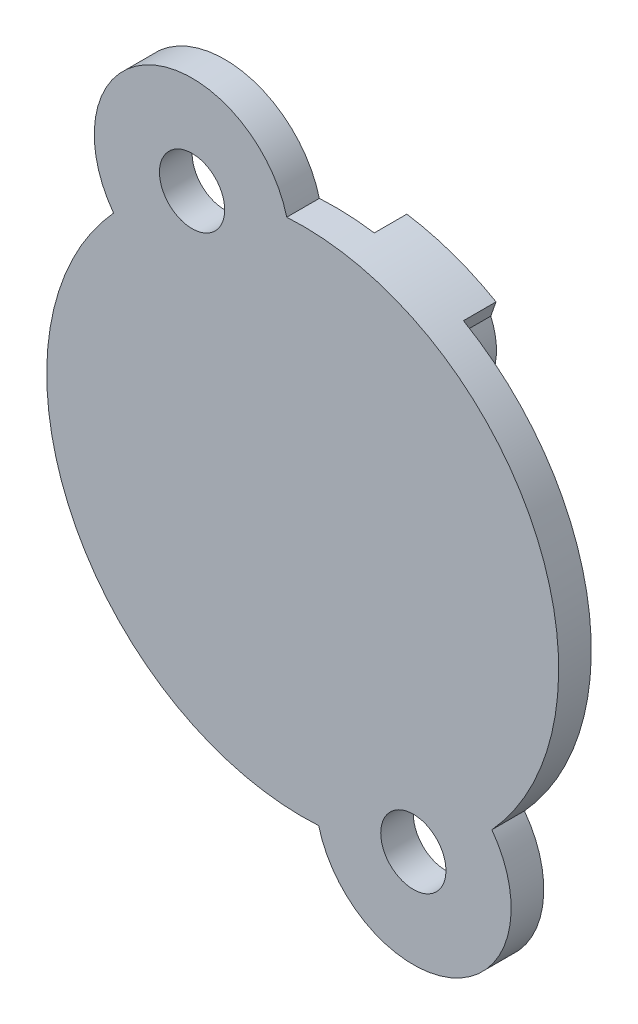
SolidWorks part; units mm, degrees
ref_plane "Front Plane" through (0, 0, 0) normal (0, 0, 1) x (1, 0, 0)
ref_plane "Top Plane" through (0, 0, 0) normal (0, 1, 0) x (1, 0, 0)
ref_plane "Right Plane" through (0, 0, 0) normal (1, 0, 0) x (0, 0, -1)
sketch "Sketch1" plane through (0, 0, 0) normal (0, 0, 1) x (1, 0, 0)
  circle A0 centre (0, 0) radius 7.85
  dimension "D1" = 15.7
extrude "Boss-Extrude1" add sketch "Sketch1" along normal blind 1
sketch "Sketch2" plane through (0, 0, 0) normal (0, 0, -1) x (-1, 0, 0)
  circle A0 centre (3.3929, 7.0789) radius 1 construction
  arc A1 (5.8006, 5.2892) -> (0.4896, 7.8347) centre (3.3929, 7.0789) ccw construction
  circle A2 centre (-3.3929, -7.0789) radius 1 construction
  arc A3 (-5.8006, -5.2892) -> (-0.4896, -7.8347) centre (-3.3929, -7.0789) ccw construction
  circle A4 centre (3.3929, 7.0789) radius 1
  arc A5 (5.8006, 5.2892) -> (0.4896, 7.8347) centre (3.3929, 7.0789) ccw
  circle A6 centre (-3.3929, -7.0789) radius 1
  arc A7 (-5.8006, -5.2892) -> (-0.4896, -7.8347) centre (-3.3929, -7.0789) ccw
  circle M1 centre (0, 0) radius 7.85
sketch "Sketch3" plane through (0, 0, 0) normal (0, 0, -1) x (-1, 0, 0)
  line L0 (-3.7675, 6.336) -> (-3.9293, 6.7958) construction
  line L1 (-3.7675, 6.336) -> (-3.9293, 6.7958)
  line L2 (-1.032, 7.2989) -> (-1.1939, 7.7587) construction
  line L3 (-1.032, 7.2989) -> (-1.1939, 7.7587)
  line L7 (1.1939, -7.7587) -> (1.032, -7.2989) construction
  line L8 (3.9293, -6.7958) -> (3.7675, -6.336) construction
  line L9 (1.1939, -7.7587) -> (1.032, -7.2989)
  line L10 (3.9293, -6.7958) -> (3.7675, -6.336)
  circle A0 centre (0, 0) radius 6
  arc A1 (-5.8006, -5.2892) -> (-0.4896, -7.8347) centre (-3.3929, -7.0789) ccw construction
  arc A2 (-5.8006, -5.2892) -> (-0.4896, -7.8347) centre (-3.3929, -7.0789) ccw
  arc A3 (5.8006, 5.2892) -> (0.4896, 7.8347) centre (3.3929, 7.0789) ccw construction
  arc A4 (5.8006, 5.2892) -> (0.4896, 7.8347) centre (3.3929, 7.0789) ccw
  circle A5 centre (3.3929, 7.0789) radius 1 construction
  circle A6 centre (3.3929, 7.0789) radius 1
  circle A7 centre (-3.3929, -7.0789) radius 1 construction
  circle A8 centre (-3.3929, -7.0789) radius 1
  circle A9 centre (0, 0) radius 7.85 construction
  circle A10 centre (0, 0) radius 7.85
  circle A11 centre (0, 0) radius 4.5
  arc A12 (-3.7675, 6.336) -> (-3.7573, 4.6779) centre (-1.9424, 5.5181) ccw construction
  arc A13 (-3.7675, 6.336) -> (-3.7573, 4.6779) centre (-1.9424, 5.5181) ccw
  arc A14 (-0.0013, 6) -> (-1.032, 7.2989) centre (-1.9424, 5.5181) ccw construction
  arc A15 (-0.0013, 6) -> (-1.032, 7.2989) centre (-1.9424, 5.5181) ccw
  arc A16 (3.7675, -6.336) -> (3.7573, -4.6779) centre (1.9424, -5.5181) ccw construction
  arc A17 (0.0013, -6) -> (1.032, -7.2989) centre (1.9424, -5.5181) ccw construction
  arc A18 (3.7675, -6.336) -> (3.7573, -4.6779) centre (1.9424, -5.5181) ccw
  arc A19 (0.0013, -6) -> (1.032, -7.2989) centre (1.9424, -5.5181) ccw
  circle M12 centre (0, 0) radius 7.85
  dimension "D1" = 9
extrude "Boss-Extrude2" add sketch "Sketch3" along normal blind 1 contours A0 A11 | A0 A19 L9 L10 A18 M12 | A0 A15 L3 L1 A13 M12 region at (2.2496, 6.3908, 0) region at (1.9358, 5.4995, 0) region at (-2.2496, -6.3908, 0)
extrude "Boss-Extrude3" add sketch "Sketch2" against normal blind 1 contours A7 A6 M1 | A5 A4 M1 region at (-3.9345, 8.2089, 0) region at (3.9345, -8.2089, 0)
extrude "Cut-Extrude1" cut sketch "Sketch2<3>" against normal blind 2 contours A4
sketch "Sketch2<3>" plane through (0, 0, 0) normal (0, 0, -1) x (-1, 0, 0) same geometry as "Sketch2"
extrude "Cut-Extrude2" cut sketch "Sketch2<4>" against normal blind 3 contours A6
sketch "Sketch2<4>" plane through (0, 0, 0) normal (0, 0, -1) x (-1, 0, 0) same geometry as "Sketch2"
sketch "Sketch4" plane through (0, 0, 1) normal (0, 0, 1) x (1, 0, 0)
  circle A0 centre (-3.3929, 7.0789) radius 1 construction
  circle A1 centre (-3.3929, 7.0789) radius 1
  circle A2 centre (3.3929, -7.0789) radius 1 construction
  circle A3 centre (3.3929, -7.0789) radius 1
  arc A4 (5.8006, -5.2892) -> (-0.4896, 7.8347) centre (0, 0) ccw
  arc A5 (-0.4896, 7.8347) -> (-5.8006, 5.2892) centre (-3.3929, 7.0789) ccw
  arc A6 (-5.8006, 5.2892) -> (0.4896, -7.8347) centre (0, 0) ccw
  arc A7 (0.4896, -7.8347) -> (5.8006, -5.2892) centre (3.3929, -7.0789) ccw
  arc A8 (5.8006, -5.2892) -> (-0.4896, 7.8347) centre (0, 0) ccw
  arc A9 (-0.4896, 7.8347) -> (-5.8006, 5.2892) centre (-3.3929, 7.0789) ccw
  arc A10 (-5.8006, 5.2892) -> (0.4896, -7.8347) centre (0, 0) ccw
  arc A11 (0.4896, -7.8347) -> (5.8006, -5.2892) centre (3.3929, -7.0789) ccw
  dimension "D2" = 7.85
  dimension "D3" = 7.85
  dimension "D4" = 3
  dimension "D5" = 2
  dimension "D6" = 7.85
  dimension "D1" = 0
